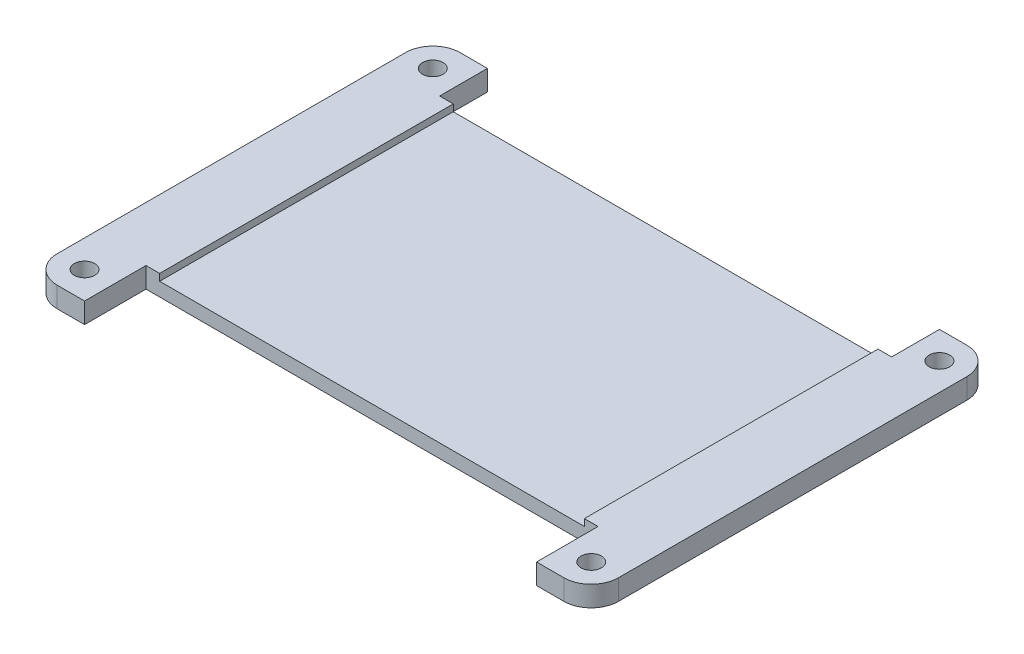
SolidWorks part; units mm, degrees
ref_plane "Front Plane" through (0, 0, 0) normal (0, 0, 1) x (1, 0, 0)
ref_plane "Top Plane" through (0, 0, 0) normal (0, 1, 0) x (1, 0, 0)
ref_plane "Right Plane" through (0, 0, 0) normal (1, 0, 0) x (0, 0, -1)
sketch "Sketch1" plane through (0, 0, 0) normal (0, 1, 0) x (1, 0, 0)
  line L0 (8, 52) -> (8, 59)
  line L1 (8, 9) -> (74.2, 9)
  line L2 (0, 0) -> (0, 59)
  line L3 (8, 52) -> (74.2, 52)
  line L4 (82.2, 0) -> (82.2, 59)
  line L5 (8, 59) -> (0, 59)
  line L6 (74.2, 52) -> (74.2, 59)
  line L7 (74.2, 59) -> (82.2, 59)
  line L8 (8, 9) -> (8, 0)
  line L9 (8, 0) -> (0, 0)
  line L10 (74.2, 9) -> (74.2, 0)
  line L11 (74.2, 0) -> (82.2, 0)
  circle A0 centre (4, 4) radius 1.5
  circle A1 centre (78.2, 4) radius 1.5
  circle A2 centre (4, 55) radius 1.5
  circle A3 centre (78.2, 55) radius 1.5
  dimension "D5" = 3
  dimension "D1" = 82.2
  dimension "D2" = 43
  dimension "D3" = 8
  dimension "D4" = 9
  dimension "D6" = 5
  dimension "D7" = 4
  dimension "D8" = 4
  dimension "D9" = 4
  dimension "D10" = 3
  dimension "D11" = 4
  dimension "D12" = 3
  dimension "D13" = 7
extrude "Boss-Extrude1" add sketch "Sketch1" along normal blind 3
sketch "Sketch2" plane through (0, 3, 0) normal (0, 1, 0) x (1, 0, 0)
  line L0 (74.2, 52) -> (8, 52) construction
  line L1 (10, 52) -> (72.2, 52)
  line L2 (10, 52) -> (10, 9)
  line L3 (10, 9) -> (72.2, 9)
  line L4 (72.2, 52) -> (72.2, 9)
  line L5 (8, 9) -> (74.2, 9) construction
  line L6 (0, 59) -> (0, 0) construction
  line L7 (82.2, 0) -> (82.2, 59) construction
  point P14 (0, 0)
  dimension "D1" = 10
  dimension "D2" = 10
extrude "Cut-Extrude1" cut sketch "Sketch2" against normal blind 1
fillet "Fillet1" radius 4 4 edges at (82.2, 1.5, -59) (82.2, 1.5, 0) (0, 1.5, 0) (0, 1.5, -59)
